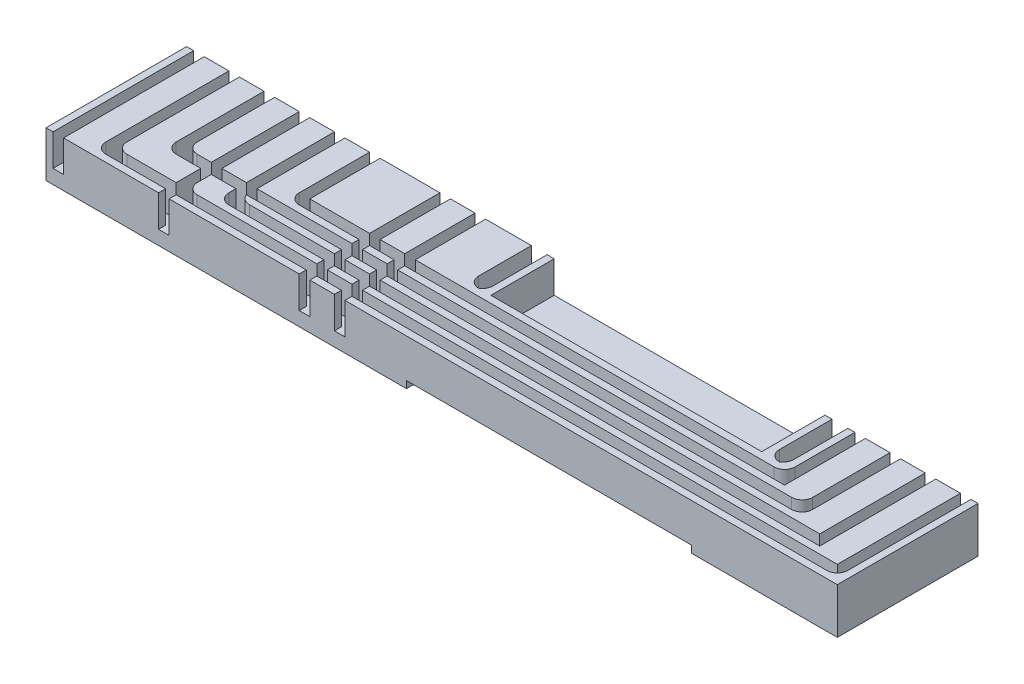
SolidWorks part; units mm, degrees
ref_plane "Front Plane" through (0, 0, 0) normal (0, 0, 1) x (1, 0, 0)
ref_plane "Top Plane" through (0, 0, 0) normal (0, 1, 0) x (1, 0, 0)
ref_plane "Right Plane" through (0, 0, 0) normal (1, 0, 0) x (0, 0, -1)
sketch "ProfileSketch1" plane through (0, 0, 0) normal (0, 1, 0) x (1, 0, 0)
  line L0 (0, 40) -> (225, 40)
  line L2 (0, 0) -> (0, 40)
  line L5 (225, 40) -> (225, 0)
  line L8 (0, 0) -> (225, 0)
  dimension "D3" = 225
  dimension "D1" = 40
extrude "ProfileBoss-Extrude1" add sketch "ProfileSketch1" along normal blind 13
sketch "Cable GuidesSketch2" plane through (0, 13, 0) normal (0, 1, 0) x (1, 0, 0)
  line L0 (0, 0) -> (225, 0) construction
  line L6 (223, 2) -> (85, 2)
  line L7 (12, 2) -> (12, 40)
  line L8 (225, 40) -> (0, 40) construction
  line L9 (12, 40) -> (15, 40)
  line L10 (15, 40) -> (15, 5)
  line L11 (15, 5) -> (32, 5)
  line L12 (0, 40) -> (0, 0) construction
  line L13 (42, 7) -> (72, 7)
  line L14 (22, 40) -> (22, 12)
  line L20 (25, 15) -> (25, 40)
  line L21 (25, 40) -> (22, 40)
  line L22 (42, 40) -> (42, 15)
  line L27 (200, 15) -> (85, 15)
  line L28 (45, 15) -> (45, 40)
  line L29 (45, 40) -> (42, 40)
  line L30 (52, 40) -> (52, 17)
  line L31 (52, 17) -> (72, 17)
  line L33 (55, 20) -> (55, 40)
  line L34 (55, 40) -> (52, 40)
  line L38 (190, 20) -> (85, 20)
  line L40 (45, 10) -> (72, 10)
  line L44 (203, 12) -> (85, 12)
  line L45 (25, 15) -> (32, 15)
  line L46 (22, 12) -> (32, 12)
  line L47 (42, 12) -> (42, 7)
  line L48 (45, 12) -> (45, 10)
  line L49 (5, 40) -> (5, 0)
  line L50 (5, 0) -> (2, 0)
  line L51 (2, 0) -> (2, 40)
  line L52 (2, 40) -> (5, 40)
  line L53 (32, 12) -> (32, 5)
  line L54 (32, 40) -> (35, 40)
  line L55 (32, 40) -> (32, 15)
  line L56 (32, 0) -> (35, 0)
  line L57 (35, 40) -> (35, 15)
  line L58 (35, 15) -> (42, 15)
  line L59 (35, 12) -> (35, 5)
  line L60 (35, 12) -> (42, 12)
  line L61 (35, 5) -> (72, 5)
  line L62 (32, 2) -> (12, 2)
  line L63 (32, 2) -> (32, 0)
  line L64 (35, 2) -> (35, 0)
  line L65 (190, 20) -> (190, 40)
  line L66 (190, 40) -> (193, 40)
  line L67 (193, 40) -> (193, 17)
  line L68 (200, 15) -> (200, 40)
  line L69 (200, 40) -> (203, 40)
  line L70 (203, 40) -> (203, 12)
  line L71 (210, 10) -> (210, 40)
  line L72 (210, 40) -> (213, 40)
  line L73 (213, 40) -> (213, 7)
  line L74 (220, 5) -> (220, 40)
  line L75 (220, 40) -> (223, 40)
  line L76 (223, 40) -> (223, 2)
  line L77 (225, 0) -> (225, 40) construction
  line L89 (72, 40) -> (72, 20)
  line L91 (72, 40) -> (75, 40)
  line L92 (75, 40) -> (75, 20)
  line L95 (82, 40) -> (82, 20)
  line L97 (85, 40) -> (85, 20)
  line L101 (82, 40) -> (85, 40)
  line L103 (82, 20) -> (75, 20)
  line L104 (98, 40) -> (102.5, 40)
  line L105 (98, 40) -> (98, 22)
  line L106 (98, 22) -> (102.5, 22)
  line L107 (102.5, 40) -> (102.5, 22)
  line L108 (183.5, 40) -> (188, 40)
  line L109 (183.5, 40) -> (183.5, 22)
  line L110 (183.5, 22) -> (188, 22)
  line L111 (188, 40) -> (188, 22)
  line L112 (104.5, 40) -> (181.5, 40)
  line L113 (104.5, 40) -> (104.5, 22)
  line L114 (104.5, 22) -> (181.5, 22)
  line L115 (181.5, 40) -> (181.5, 22)
  line L116 (82, 17) -> (82, 15)
  line L117 (85, 17) -> (85, 15)
  line L118 (75, 17) -> (75, 15)
  line L119 (72, 20) -> (55, 20)
  line L120 (72, 17) -> (72, 15)
  line L121 (85, 12) -> (85, 10)
  line L122 (82, 15) -> (75, 15)
  line L123 (82, 12) -> (82, 10)
  line L124 (85, 17) -> (193, 17)
  line L125 (75, 12) -> (75, 10)
  line L126 (72, 15) -> (45, 15)
  line L127 (72, 12) -> (72, 10)
  line L128 (75, 17) -> (82, 17)
  line L129 (85, 7) -> (85, 5)
  line L130 (85, 10) -> (210, 10)
  line L131 (82, 7) -> (82, 5)
  line L132 (82, 12) -> (75, 12)
  line L133 (75, 7) -> (75, 5)
  line L134 (75, 10) -> (82, 10)
  line L135 (72, 7) -> (72, 5)
  line L136 (72, 12) -> (45, 12)
  line L137 (85, 2) -> (85, 0)
  line L138 (85, 5) -> (220, 5)
  line L139 (82, 2) -> (82, 0)
  line L140 (85, 7) -> (213, 7)
  line L141 (75, 2) -> (75, 0)
  line L142 (72, 2) -> (72, 0)
  line L143 (75, 5) -> (82, 5)
  line L144 (75, 7) -> (82, 7)
  line L145 (72, 2) -> (35, 2)
  line L146 (82, 2) -> (75, 2)
  line L147 (72, 0) -> (75, 0)
  line L148 (82, 0) -> (85, 0)
  dimension "D15" = 2
  dimension "D16" = 7
  dimension "D2" = 2
  dimension "D4" = 7
  dimension "D8" = 2
  dimension "D6" = 2
  dimension "D5" = 3
  dimension "D9" = 7
  dimension "D7" = 7
  dimension "D10" = 7
  dimension "D3" = 2
  dimension "D11" = 7
  dimension "D12" = 2
  dimension "D13" = 7
  dimension "D14" = 7
  dimension "D18" = 3
  dimension "D19" = 3
  dimension "D20" = 3
  dimension "D21" = 3
  dimension "D31" = 7
  dimension "D33" = 4.5
  dimension "D34" = 2
  dimension "D35" = 2
  dimension "D36" = 2
  dimension "D17" = 17
  dimension "D22" = 13
extrude "CableGuidesCut-Extrude1" cut sketch "Cable GuidesSketch2" against normal blind 9
fillet "Fillet3" radius 3 6 edges at (22, 8.5, -12) (42, 8.5, -7) (52, 8.5, -17) (12, 8.5, -2) (98, 8.5, -22) (183.5, 8.5, -22)
fillet "Fillet5" radius 3 4 edges at (200, 8.5, -15) (190, 8.5, -20) (188, 8.5, -22) (102.5, 8.5, -22)
fillet "Fillet6" radius 3 2 edges at (223, 8.5, -2) (203, 8.5, -12)
fillet "Fillet7" radius 3 4 edges at (35, 8.5, -5) (45, 8.5, -10) (15, 8.5, -5) (25, 8.5, -15)
sketch "BridgeSketch2" plane through (0, 0, 0) normal (0, 0, 1) x (1, 0, 0)
  line L0 (0, 0) -> (225, 0) construction
  line L1 (102.5, 2) -> (183.5, 2)
  line L2 (102.5, 2) -> (102.5, 0)
  line L3 (102.5, 0) -> (183.5, 0)
  line L4 (183.5, 2) -> (183.5, 0)
  dimension "D1" = 2
extrude "BridgeCut-Extrude3" cut sketch "BridgeSketch2" against normal through all
sketch "MountHolesSketch4" plane through (0, 4, 0) normal (0, 1, 0) x (1, 0, 0)
  line L0 (98, 40) -> (98, 25) construction
  line L1 (183.5, 40) -> (183.5, 25) construction
  line L2 (183.5, 40) -> (181.5, 40) construction
  circle A0 centre (100.25, 30.2278) radius 1.592
  circle A1 centre (185.75, 30) radius 1.6518
  dimension "D1" = 2.25
  dimension "D2" = 2.25
  dimension "D3" = 10
extrude "MountHolesCut-Extrude4" cut sketch "MountHolesSketch4" against normal through all
equation "\"PowerCableGuideSupplyWidth\"= \"DistanceBetweenPowerSupplyLeads\" * \"NumberOfPowerLeads\" + \"DistanceBetweenPowerSupplyAndOctopus\" + \"DistanceBetweenPowerSupplyLeads\" * \"NumperOfOctopusLeads\""
equation "\"PowerCableGuideHeight\"= 40mm"
equation "\"PowerCableDiameter\"= 3mm"
equation "\"NumberOfPowerLeads\"= 9"
equation "\"D1@CableGuidesCut-Extrude1\"=\"PowerCableGuideDepth\" - \"PowerGuidebaseThickness\""
equation "\"M3HoleDiameter\"= 3mm"
equation "\"DistanceBetweenPowerSupplyLeads\"= 10mm'Spec"
equation "\"D3@ProfileSketch1\"=\"PowerCableGuideSupplyWidth\""
equation "\"D16@Cable GuidesSketch2\"=\"DistanceBetweenPowerSupplyLeads\"-\"PowerCableDiameter\""
equation "\"PowerCableGuideDepth\"= 13mm"
equation "\"D1@ProfileBoss-Extrude1\"=\"PowerCableGuideDepth\""
equation "\"D1@ProfileSketch1\"=\"PowerCableGuideHeight\""
equation "\"D4@Cable GuidesSketch2\"=\"DistanceBetweenPowerSupplyLeads\" - \"PowerCableDiameter\""
equation "\"D9@Cable GuidesSketch2\"=\"DistanceBetweenPowerSupplyLeads\" - \"PowerCableDiameter\""
equation "\"D7@Cable GuidesSketch2\"=\"DistanceBetweenPowerSupplyLeads\" - \"PowerCableDiameter\""
equation "\"D10@Cable GuidesSketch2\"=\"DistanceBetweenPowerSupplyLeads\"-\"PowerCableDiameter\""
equation "\"NumperOfOctopusLeads\"= 4"
equation "\"DistanceBetweenPowerSupplyAndOctopus\"= 95mm"
equation "\"D3@Cable GuidesSketch2\"=2mm"
equation "\"D11@Cable GuidesSketch2\"=\"DistanceBetweenPowerSupplyLeads\" - \"PowerCableDiameter\""
equation "\"D13@Cable GuidesSketch2\"=\"DistanceBetweenPowerSupplyLeads\" - \"PowerCableDiameter\""
equation "\"D14@Cable GuidesSketch2\"=\"DistanceBetweenPowerSupplyLeads\" - \"PowerCableDiameter\""
equation "\"D18@Cable GuidesSketch2\"=\"PowerCableDiameter\""
equation "\"D19@Cable GuidesSketch2\"=\"PowerCableDiameter\""
equation "\"D20@Cable GuidesSketch2\"=\"PowerCableDiameter\""
equation "\"D21@Cable GuidesSketch2\"=\"PowerCableDiameter\""
equation "\"PowerGuideBridgeHeight\"= 2mm"
equation "\"PowerGuidebaseThickness\"= \"PowerGuideBridgeHeight\" + 2mm"
equation "\"D31@Cable GuidesSketch2\"=\"DistanceBetweenPowerSupplyLeads\"-\"PowerCableDiameter\""
equation "\"D33@Cable GuidesSketch2\"=\"M3HoleDiameter\"*1.5"
equation "\"D1@MountHolesSketch4\" = \"M3HoleDiameter\" * 1.5 / 2"
equation "\"D2@MountHolesSketch4\" = \"M3HoleDiameter\" * 1.5 / 2"
equation "\"D17@Cable GuidesSketch2\"=\"DistanceBetweenPowerSupplyLeads\"*2 - \"PowerCableDiameter\""
equation "\"D22@Cable GuidesSketch2\"=\"DistanceBetweenPowerSupplyLeads\"+\"PowerCableDiameter\""
